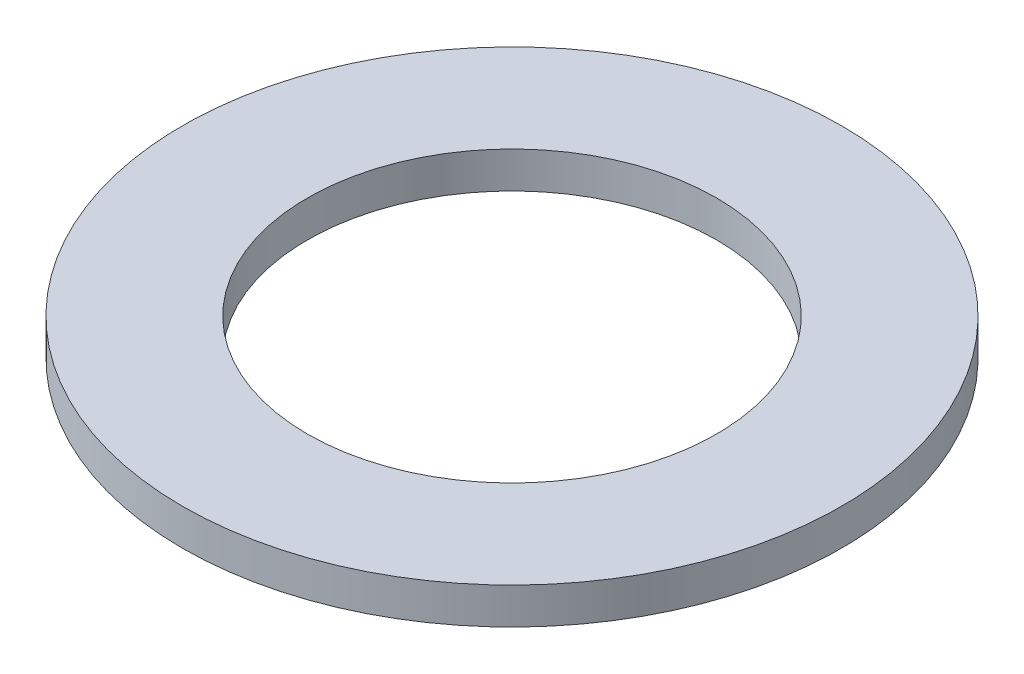
SolidWorks part; units mm, degrees
ref_plane "Front Plane" through (0, 0, 0) normal (0, 0, 1) x (1, 0, 0)
ref_plane "Top Plane" through (0, 0, 0) normal (0, 1, 0) x (1, 0, 0)
ref_plane "Right Plane" through (0, 0, 0) normal (1, 0, 0) x (0, 0, -1)
sketch "Sketch1" plane through (0, 0, 0) normal (0, 1, 0) x (1, 0, 0)
  circle A0 centre (0, 0) radius 72.5
  dimension "FLANGE_OD" = 145
extrude "Boss-Extrude1" add sketch "Sketch1" along normal blind 8
sketch "Sketch2" plane through (0, 0, 0) normal (0, 1, 0) x (1, 0, 0)
  circle A0 centre (0, 0) radius 45
  dimension "BORE_D" = 90
extrude "Cut-Extrude1" cut sketch "Sketch2" along normal through all
sketch "Sketch3" plane through (0, 8, 0) normal (0, 1, 0) x (1, 0, 0)
  circle A0 centre (0, 0) radius 31.4853 construction
  circle A1 centre (-31.4853, 0) radius 4.319
  dimension "BOLT_D" = 8.638
  dimension "BOLT_PCD" = 62.9707
extrude "Cut-Extrude2" cut sketch "Sketch3" against normal blind 7.583 rebuild error yes
pattern_circular "CirPattern1" count 6 over 360 rebuild error yes
